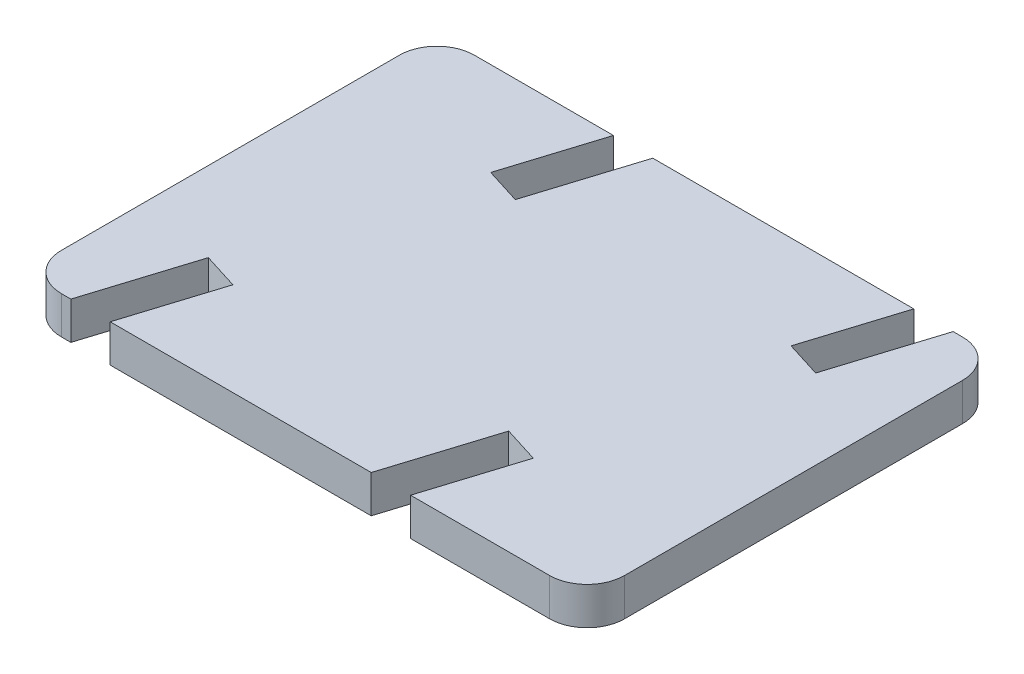
SolidWorks part; units mm, degrees
material "Acrylic (Medium-high impact)"
ref_plane "Front Plane" through (0, 0, 0) normal (0, 0, 1) x (1, 0, 0)
ref_plane "Top Plane" through (0, 0, 0) normal (0, 1, 0) x (1, 0, 0)
ref_plane "Right Plane" through (0, 0, 0) normal (1, 0, 0) x (0, 0, -1)
sketch "Sketch1" plane through (0, 0, 0) normal (0, 1, 0) x (1, 0, 0)
  line L0 (23.5073, 55) -> (19.6047, 42.5605)
  line L1 (5, 0) -> (6.2524, 0)
  line L2 (0, 5) -> (0, 50)
  line L3 (5, 55) -> (23.5073, 55)
  line L4 (75, 5) -> (75, 50)
  line L5 (28.7476, 55) -> (63.5073, 55)
  line L6 (19.6047, 42.5605) -> (24.3755, 41.0638)
  line L7 (28.7476, 55) -> (24.3755, 41.0638)
  line L8 (63.5073, 55) -> (59.6047, 42.5605)
  line L9 (68.7476, 55) -> (70, 55)
  line L10 (6.2524, 0) -> (10.6245, 13.9362)
  line L11 (59.6047, 42.5605) -> (64.3755, 41.0638)
  line L12 (68.7476, 55) -> (64.3755, 41.0638)
  line L13 (10.6245, 13.9362) -> (15.3953, 12.4395)
  line L14 (15.3953, 12.4395) -> (11.4927, 0)
  line L15 (11.4927, 0) -> (46.2524, 0)
  line L16 (46.2524, 0) -> (50.6245, 13.9362)
  line L17 (50.6245, 13.9362) -> (55.3953, 12.4395)
  line L18 (55.3953, 12.4395) -> (51.4927, 0)
  line L19 (51.4927, 0) -> (70, 0)
  line L20 (0, 27.5) -> (75, 27.5) construction
  line L21 (19.6047, 42.5605) -> (19.6047, 27.5) construction
  line L22 (15.3953, 12.4395) -> (15.3953, 27.5) construction
  line L23 (37.5, 27.5) -> (37.5, 55) construction
  line L24 (37.5, 27.5) -> (37.5, 0) construction
  line L25 (24.3755, 41.0638) -> (37.5, 41.0638) construction
  line L26 (50.6245, 13.9362) -> (37.5, 13.9362) construction
  arc A0 (70, 55) -> (75, 50) centre (70, 50) cw
  arc A1 (70, 0) -> (75, 5) centre (70, 5) ccw
  arc A2 (5, 0) -> (0, 5) centre (5, 5) cw
  arc A3 (0, 50) -> (5, 55) centre (5, 50) cw
  point P5 (21.9901, 41.8122)
  point P8 (61.9901, 41.8122)
  point P19 (75, 0)
  point P22 (0, 0)
  point P25 (0, 55)
  dimension "D3" = 5
  dimension "D1" = 5
  dimension "D2" = 75
  dimension "D4" = 30
  dimension "D5" = 40
  dimension "D6" = 55
  dimension "D10" = 17.418
extrude "Boss-Extrude1" add sketch "Sketch1" along normal blind 5
